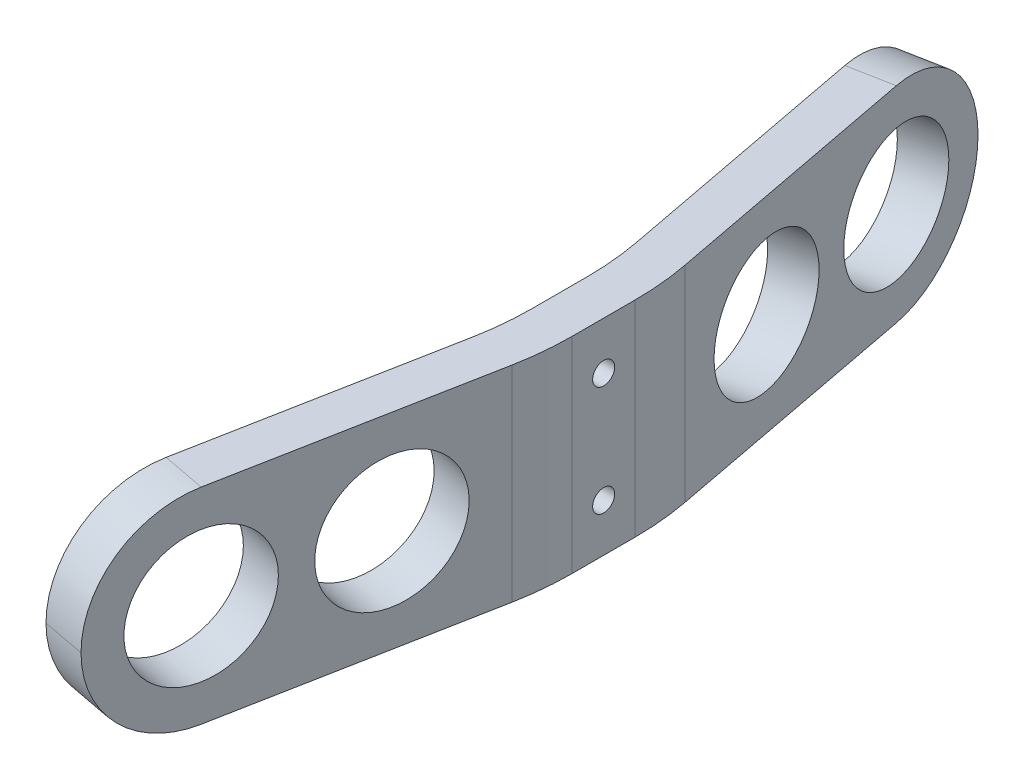
SolidWorks part; units mm, degrees
ref_plane "Front" through (0, 0, 0) normal (0, 0, 1) x (1, 0, 0)
ref_plane "Top" through (0, 0, 0) normal (0, 1, 0) x (1, 0, 0)
ref_plane "Right" through (0, 0, 0) normal (1, 0, 0) x (0, 0, -1)
sketch "Sketch1" plane through (0, 0, 0) normal (0, 1, 0) x (1, 0, 0)
  line L0 (0, -60) -> (0, 60) construction
  line L1 (0, 60) -> (10, 7.5)
  line L2 (10, 7.5) -> (10, -7.5)
  line L3 (10, -7.5) -> (0, -60)
  line L4 (0, 0) -> (10, 0) construction
  line L5 (5.894, 61.1227) -> (16, 8.0663)
  line L6 (16, 8.0663) -> (16, -8.0663)
  line L7 (16, -8.0663) -> (5.894, -61.1227)
  line L8 (0, 60) -> (5.894, 61.1227)
  line L9 (0, -60) -> (5.894, -61.1227)
  dimension "D1" = 120
  dimension "D2" = 10
  dimension "D3" = 15
  dimension "D4" = 6
extrude "Boss-Extrude1" add sketch "Sketch1" along normal blind 28
fillet "Fillet1" radius 40 4 edges at (10, 14, 7.5) (10, 14, -7.5) (16, 14, -8.0663) (16, 14, 8.0663)
sketch "Sketch2" plane through (16.9225, 0, 3.2233) normal (0.9823, 0, 0.1871) x (0.1871, 0, -0.9823)
  line L0 (-58.9403, 14) -> (-8.7057, 14) construction
  line L1 (-58.9403, 28) -> (-58.9403, 0) construction
  line L2 (-8.7057, 0) -> (-8.7057, 28) construction
  circle A0 centre (-44.9403, 14) radius 9
  circle A1 centre (-22.7057, 14) radius 9
  point P10 (-47.223, 15)
  point P11 (-23.3637, 15)
  dimension "D1" = 18
  dimension "D2" = 18
  dimension "D3" = 14
  dimension "D4" = 14
extrude "Cut-Extrude1" cut sketch "Sketch2" against normal up to next
mirror "Mirror1" about plane through (0, 0, 0) normal (0, 0, 1) of "Cut-Extrude1"
sketch "Sketch3" plane through (16, 0, 0) normal (1, 0, 0) x (0, 0, -1)
  line L0 (0, 21.5) -> (0, 6.5) construction
  line L1 (-4.2908, 14) -> (4.2908, 14) construction
  line L2 (-4.2908, 28) -> (-4.2908, 0) construction
  line L3 (4.2908, 0) -> (4.2908, 28) construction
  circle A0 centre (0, 21.5) radius 1.5
  circle A1 centre (0, 6.5) radius 1.5
  point P11 (0, 14)
  point P12 (0, 14)
  dimension "D1" = 3
  dimension "D2" = 3
  dimension "D3" = 15
extrude "Cut-Extrude2" cut sketch "Sketch3" against normal up to next
fillet "Fillet2" radius 14 4 edges at (2.947, 0, -60.5613) (2.947, 28, -60.5613) (2.947, 0, 60.5613) (2.947, 28, 60.5613)
